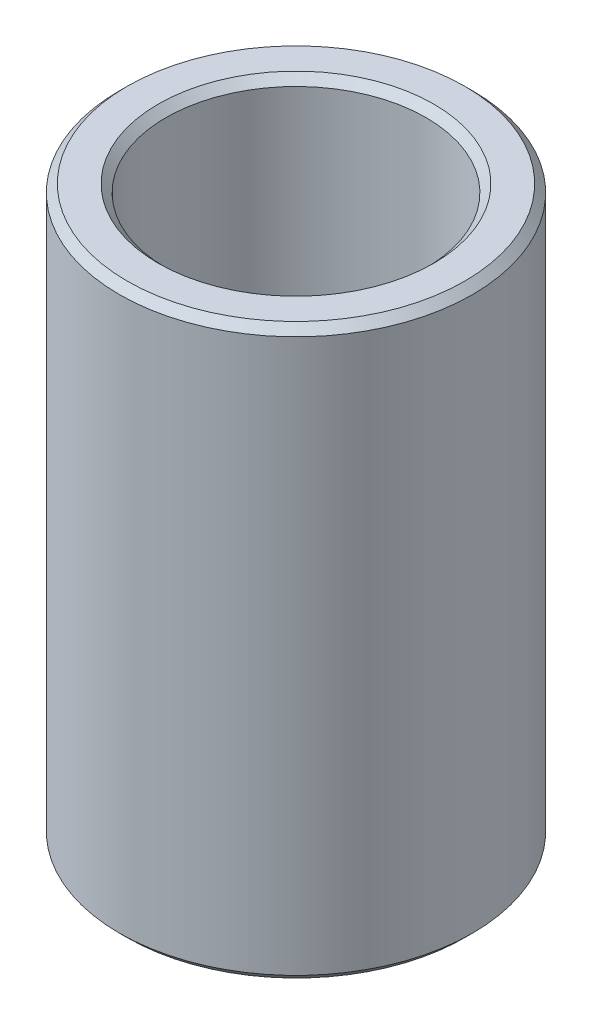
SolidWorks part; units mm, degrees
ref_plane "Front Plane" through (0, 0, 0) normal (0, 0, 1) x (1, 0, 0)
ref_plane "Top Plane" through (0, 0, 0) normal (0, 1, 0) x (1, 0, 0)
ref_plane "Right Plane" through (0, 0, 0) normal (1, 0, 0) x (0, 0, -1)
sketch "Sketch1" plane through (0, 0, 0) normal (0, 1, 0) x (1, 0, 0)
  circle A0 centre (0, 0) radius 57.5
  dimension "SLEEVE_OD" = 115
extrude "Boss-Extrude1" add sketch "Sketch1" along normal blind 185.1841
sketch "Sketch2" plane through (0, 0, 0) normal (0, 1, 0) x (1, 0, 0)
  circle A0 centre (0, 0) radius 42.3591
  dimension "BORE_D" = 84.7181
extrude "Cut-Extrude1" cut sketch "Sketch2" along normal through all
chamfer "Chamfer1" distance 2.5346 angle 45 4 edges at (0, 185.1841, 42.3591) (0, 0, 42.3591) (0, 0, 57.5) (0, 185.1841, 57.5)
